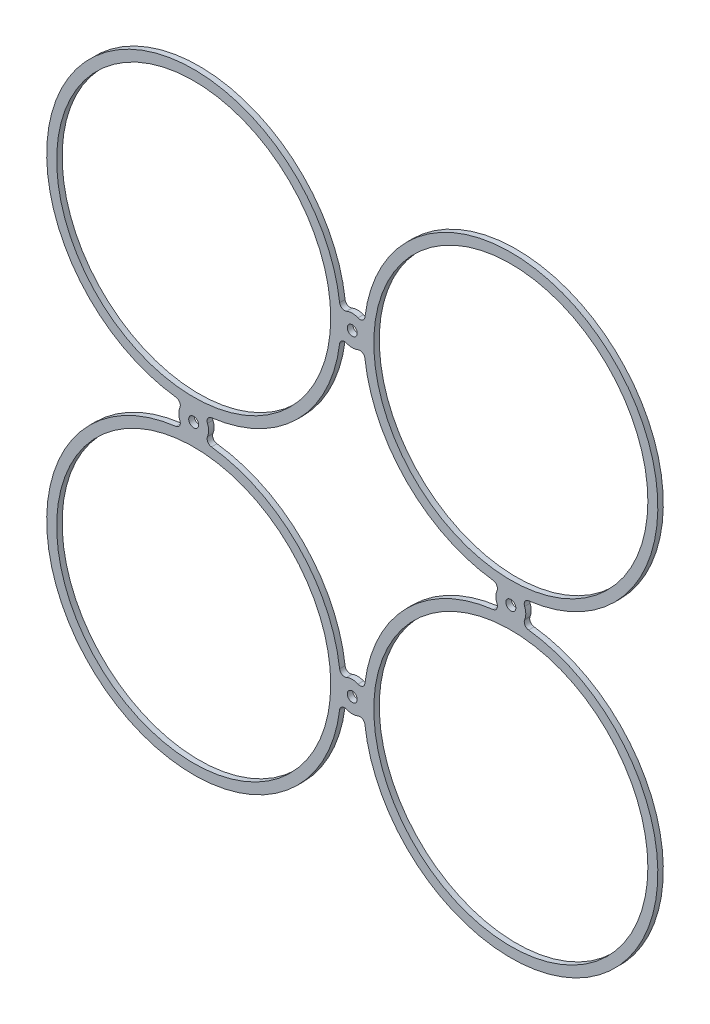
SolidWorks part; units mm, degrees
material "Hexcel AS4C (3000 Filaments)"
ref_plane "Front Plane" through (0, 0, 0) normal (0, 0, 1) x (1, 0, 0)
ref_plane "Top Plane" through (0, 0, 0) normal (0, 1, 0) x (1, 0, 0)
ref_plane "Right Plane" through (0, 0, 0) normal (1, 0, 0) x (0, 0, -1)
sketch "Sketch1" plane through (0, 0, 0) normal (0, 0, 1) x (1, 0, 0)
  line L0 (0, -18.1806) -> (0, 16.1577) construction
  line L1 (-47.1416, 0) -> (36.9217, 0) construction
  line L2 (-4.3198, 31.8198) -> (-2.3198, 31.8198) construction
  line L3 (-31.8198, 2.3198) -> (-31.8198, -2.3198) construction
  line L4 (-31.8198, -31.8198) -> (31.8198, 31.8198) construction
  line L5 (-31.8198, 1) -> (-31.8198, 3) construction
  line L6 (-31.8198, 31.8198) -> (31.8198, -31.8198) construction
  circle A0 centre (-31.8198, 31.8198) radius 27.5
  circle A2 centre (31.8198, -31.8198) radius 5.125 construction
  circle A3 centre (-31.8198, 31.8198) radius 29.5
  circle A4 centre (31.8198, 31.8198) radius 29.5
  circle A5 centre (31.8198, 31.8198) radius 27.5
  circle A6 centre (31.8198, -31.8198) radius 27.5
  circle A7 centre (31.8198, -31.8198) radius 29.5
  circle A8 centre (-31.8198, -31.8198) radius 29.5
  circle A9 centre (-31.8198, -31.8198) radius 27.5
  circle A10 centre (-31.8198, 0) radius 1
  circle A11 centre (-31.8198, 0) radius 3
  circle A12 centre (-53.3866, 53.3866) radius 1
  circle A13 centre (-53.3866, 53.3866) radius 3
  circle A14 centre (53.3866, 53.3866) radius 3
  circle A15 centre (53.3866, 53.3866) radius 1
  circle A16 centre (53.3866, -53.3866) radius 3
  circle A17 centre (53.3866, -53.3866) radius 1
  circle A19 centre (-53.3866, -53.3866) radius 3
  circle A20 centre (-53.3866, -53.3866) radius 1
  circle A21 centre (31.8198, 0) radius 3
  circle A22 centre (31.8198, 0) radius 1
  circle A23 centre (0, 31.8198) radius 3
  circle A24 centre (0, 31.8198) radius 1
  circle A25 centre (0, -31.8198) radius 1
  circle A26 centre (0, -31.8198) radius 3
  dimension "D1" = 55
  dimension "D2" = 2
  dimension "D3" = 2
extrude "Boss-Extrude1" add sketch "Sketch1" along normal blind 1.1 contours A3 A13 | A3 A23 A13 A0 A11 | A4 A23 A21 A14 A5 | A14 A4 | A26 A7 A16 A6 A21 | A21 A7 A4 A22 | A21 A7 | A21 A4 | A7 A16 | A7 A26 | A7 A26 A8 A25 | A8 A26 | A26 A8 A11 A19 A9 | A19 A8 | A3 A11 A8 A10 | A8 A11 | A3 A11 | A23 A4 | A23 A4 A3 A24 | A23 A3 region at (-50.5379, 52.2066, 0) region at (-52.0763, 52.0763, 0) region at (-31.8198, 2.6059, 0) region at (-31.8198, 2.2433, 0) region at (-31.8198, -3.8336, 0) region at (-31.8198, -2.6059, 0) region at (0, 34.7433, 0) region at (-2.6059, 31.8198, 0) region at (-52.0763, -52.0763, 0) region at (2.6059, 31.8198, 0) region at (20.4243, 58.1239, 0) region at (0, -28.8964, 0) region at (-2.6059, -31.8198, 0) region at (52.0763, 52.0763, 0) region at (31.8198, 2.6059, 0) region at (31.8198, 2.2433, 0) region at (2.6059, -31.8198, 0) region at (11.5496, -11.5496, 0) region at (31.8198, -2.6059, 0) region at (52.0763, -52.0763, 0)
fillet "Fillet1" radius 1 16 edges at (2.3767, -29.9891, 0.55) (-2.3767, -29.9891, 0.55) (29.9891, 2.3767, 0.55) (29.9891, -2.3767, 0.55) (2.3767, 29.9891, 0.55) (-2.3767, 29.9891, 0.55) (-29.9891, 2.3767, 0.55) (-29.9891, -2.3767, 0.55) (33.6505, -2.3767, 0.55) (33.6505, 2.3767, 0.55) (-2.3767, 33.6505, 0.55) (2.3767, 33.6505, 0.55) (-33.6505, 2.3767, 0.55) (-33.6505, -2.3767, 0.55) (2.3767, -33.6505, 0.55) (-2.3767, -33.6505, 0.55)
